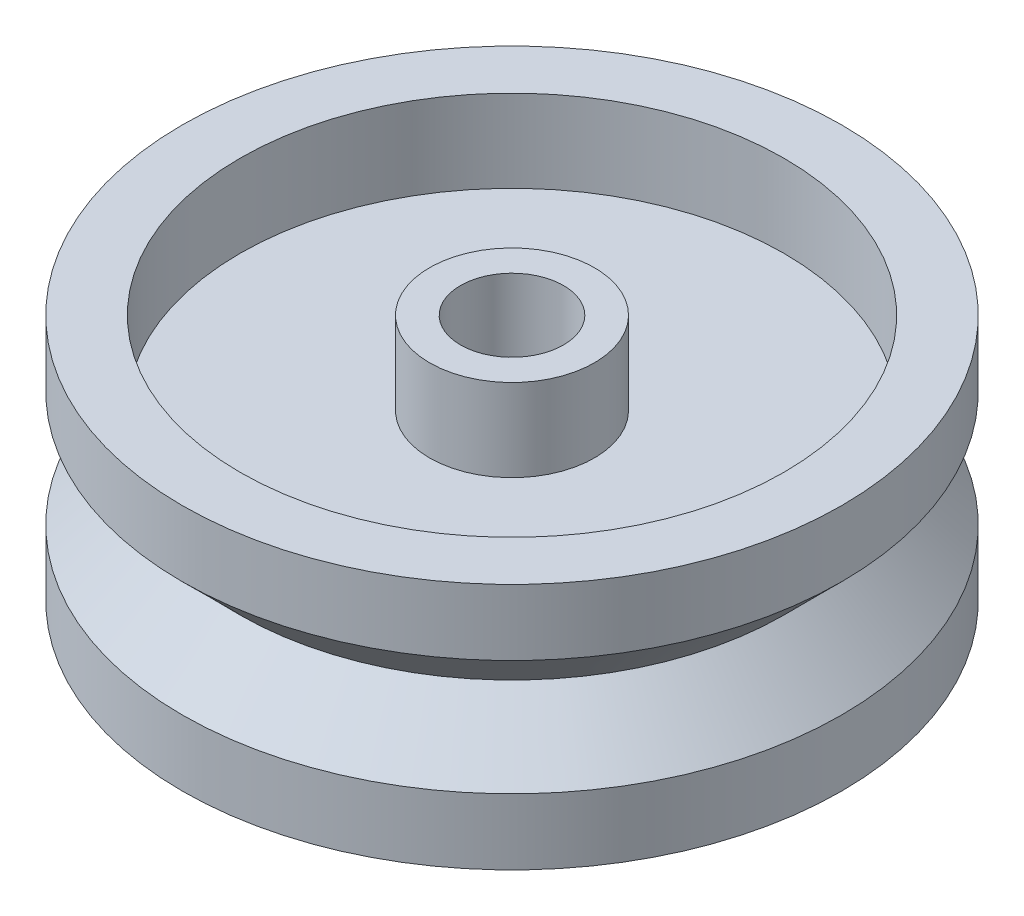
SolidWorks part; units mm, degrees
ref_plane "Front Plane" through (0, 0, 0) normal (1, 0, 0) x (0, 1, 0)
ref_plane "Top Plane" through (0, 0, 0) normal (0, 0, 1) x (0, 1, 0)
ref_plane "Right Plane" through (0, 0, 0) normal (0, 1, 0) x (-1, 0, 0)
sketch "Sketch1" plane through (0, 0, 0) normal (0, 1, 0) x (-1, 0, 0)
  circle A0 centre (0, 0) radius 3.125
  circle A1 centre (0, 0) radius 5
  circle A2 centre (0, 0) radius 16.5
  circle A3 centre (0, 0) radius 20
  dimension "D1" = 6.25
  dimension "D2" = 10
  dimension "D3" = 33
  dimension "D4" = 40
extrude "Boss-Extrude1" add sketch "Sketch1" along normal blind 7.5 and the other way blind 7.5 contours A3 A2 | A1 A0 region at (4.8586, 0, 0) region at (19.4343, 0, 0)
extrude "Boss-Extrude2" add sketch "Sketch1<3>" along normal blind 2.5 and the other way blind 2.5 contours A2 A1 region at (16.0333, 0, 0)
sketch "Sketch1<3>" plane through (0, 0, 0) normal (0, 1, 0) x (-1, 0, 0) same geometry as "Sketch1"
sketch "Sketch2" plane through (0, 0, 0) normal (0, 0, 1) x (0, 1, 0)
  line L0 (-9.9802, 0) -> (9.3185, 0) construction
  line L1 (3.5, 20) -> (0, 16.5)
  line L2 (7.5, 20) -> (-7.5, 20) construction
  line L3 (7.5, -20) -> (7.5, 20) construction
  line L4 (0, 20) -> (0, -20) construction
  line L5 (-7.5, -20) -> (7.5, -20) construction
  line L6 (-3.5, 20) -> (0, 16.5)
  line L7 (-3.5, 20) -> (3.5, 20)
  line L8 (-3.5, -20) -> (3.5, -20)
  line L9 (3.5, -20) -> (0, -16.5)
  line L10 (-3.5, -20) -> (0, -16.5)
  dimension "D1" = 4
  dimension "D2" = 45
revolve "Cut-Revolve1" cut sketch "Sketch2" angle 360 about L0
